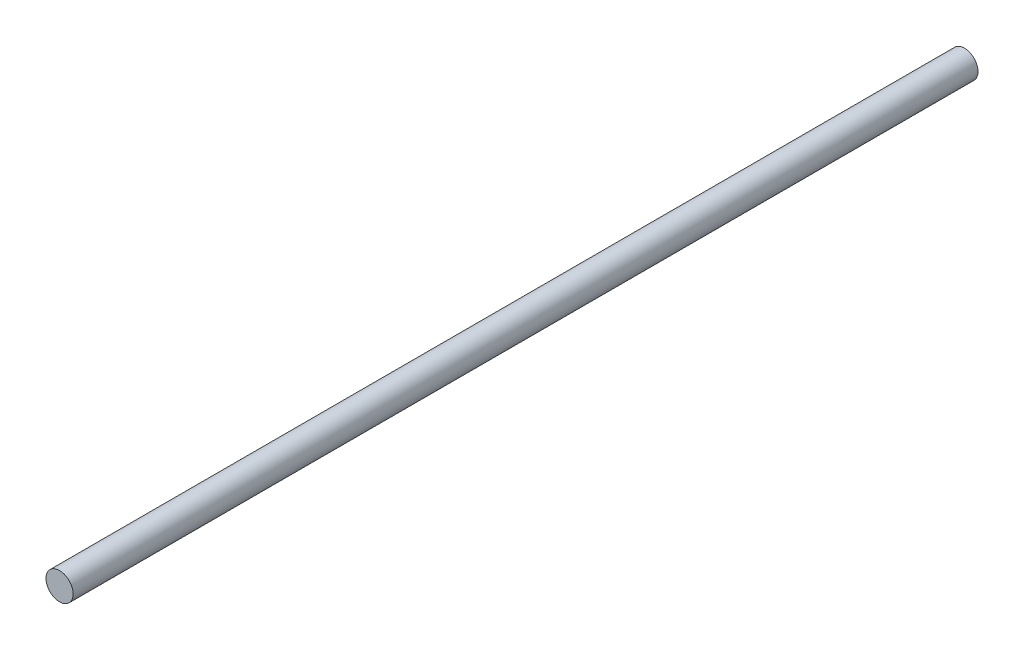
SolidWorks part; units mm, degrees
ref_plane "Спереди" through (0, 0, 0) normal (0, 0, 1) x (1, 0, 0)
ref_plane "Сверху" through (0, 0, 0) normal (0, 1, 0) x (1, 0, 0)
ref_plane "Справа" through (0, 0, 0) normal (1, 0, 0) x (0, 0, -1)
sketch "Эскиз1" plane through (0, 0, 0) normal (0, 0, 1) x (1, 0, 0)
  circle A0 centre (0, 0) radius 3
  dimension "D1" = 6
extrude "Бобышка-Вытянуть1" add sketch "Эскиз1" along normal blind 100 and the other way blind 100
